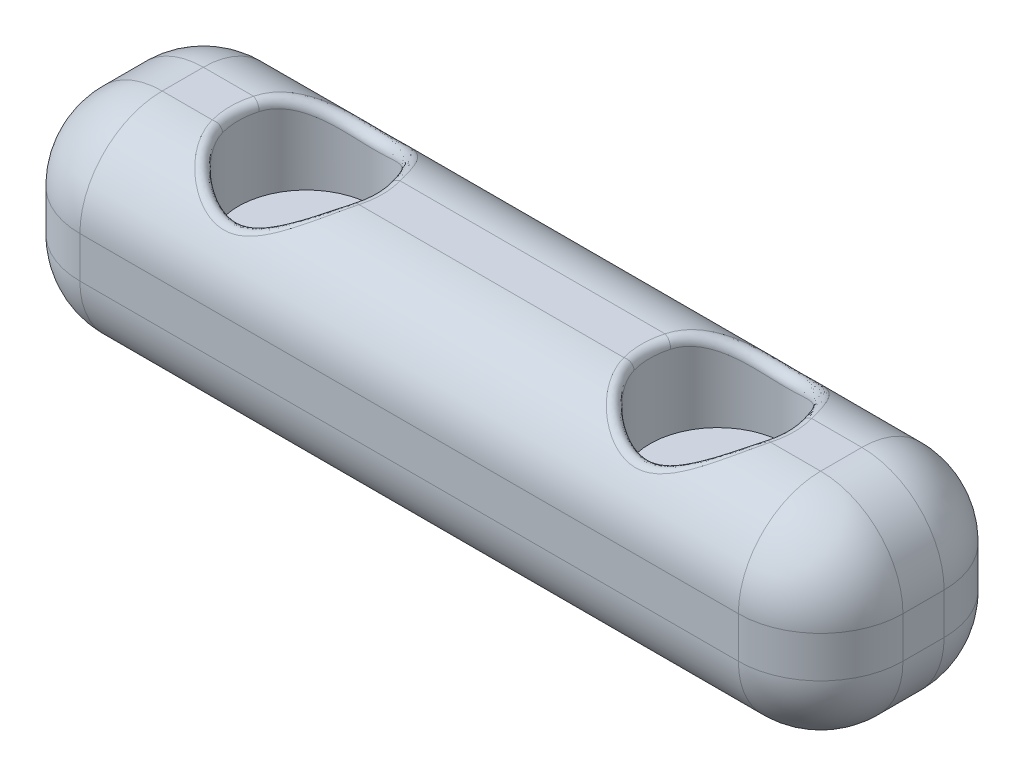
SolidWorks part; units mm, degrees
ref_plane "Front Plane" through (0, 0, 0) normal (0, 0, 1) x (1, 0, 0)
ref_plane "Top Plane" through (0, 0, 0) normal (0, 1, 0) x (1, 0, 0)
ref_plane "Right Plane" through (0, 0, 0) normal (1, 0, 0) x (0, 0, -1)
sketch "Sketch1" plane through (0, 0, 0) normal (0, 1, 0) x (1, 0, 0)
  line L1 (-9.1379, 3.1466) -> (10.8621, 3.1466)
  line L2 (-9.1379, 3.1466) -> (-9.1379, -1.8534)
  line L3 (-9.1379, -1.8534) -> (10.8621, -1.8534)
  line L4 (10.8621, 3.1466) -> (10.8621, -1.8534)
  dimension "D1" = 5
  dimension "D2" = 20
extrude "Boss-Extrude1" add sketch "Sketch1" along normal blind 5
sketch "Sketch2" plane through (0, 5, 0) normal (0, 1, 0) x (1, 0, 0)
  line L0 (-9.1379, 0.6466) -> (10.8621, 0.6466) construction
  line L1 (-9.1379, 3.1466) -> (-9.1379, -1.8534) construction
  line L2 (10.8621, -1.8534) -> (10.8621, 3.1466) construction
  line L3 (0.8621, 0.6466) -> (-9.1379, 0.6466) construction
  line L4 (0.8621, 0.6466) -> (10.8621, 0.6466) construction
  circle A0 centre (-4.1379, 0.6466) radius 1.65
  circle A1 centre (5.8621, 0.6466) radius 1.65
  dimension "D1" = 5
  dimension "D2" = 5
extrude "Cut-Extrude1" cut sketch "Sketch2" against normal blind 2
fillet "Fillet1" radius 2 12 edges at (0.8621, 0, 1.8534) (0.8621, 0, -3.1466) (-9.1379, 0, -0.6466) (10.8621, 2.5, 1.8534) (10.8621, 5, -0.6466) (10.8621, 2.5, -3.1466) (10.8621, 0, -0.6466) (-9.1379, 2.5, -3.1466) (-9.1379, 2.5, 1.8534) (-9.1379, 5, -0.6466) (0.8621, 5, 1.8534) (0.8621, 5, -3.1466)
fillet "Fillet2" radius 0.2 8 edges at (7.5121, 5, -0.6466) (5.8048, 4.637, 1.0025) (4.2121, 5, -0.6466) (-2.4879, 5, -0.6466) (-4.1952, 4.637, 1.0025) (-5.7879, 5, -0.6466) (5.9194, 4.637, -2.2956) (-4.0806, 4.637, -2.2956)
